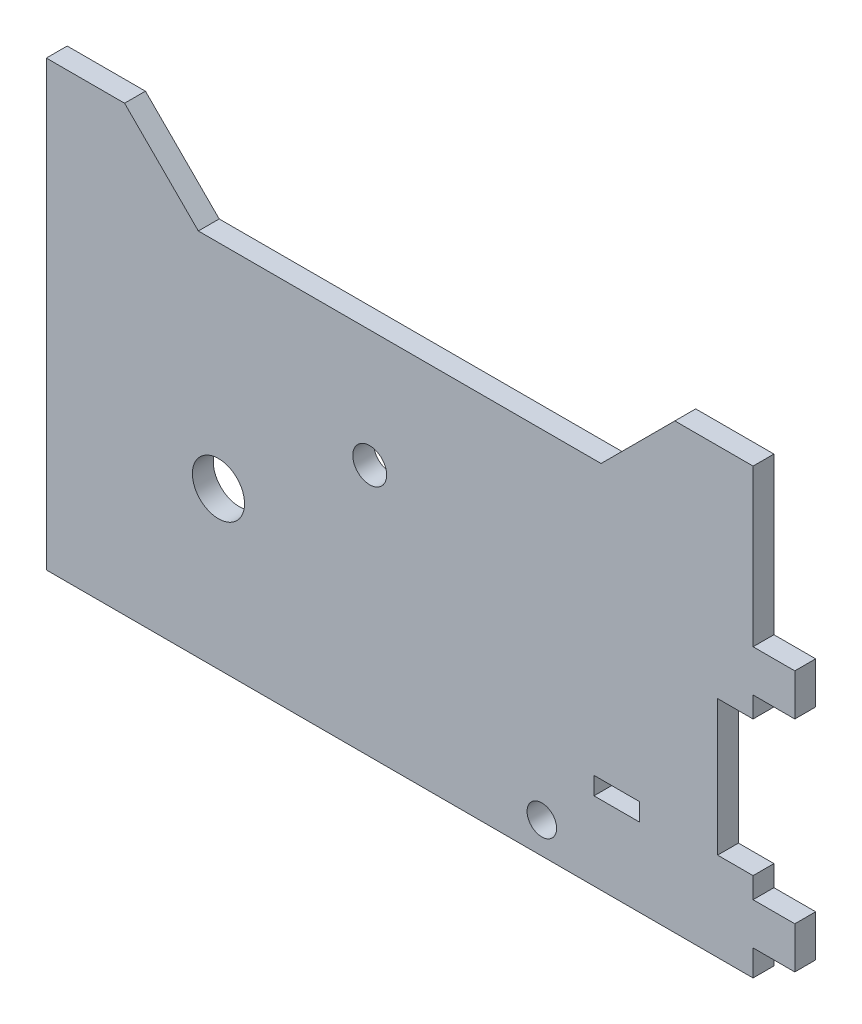
SolidWorks part; units mm, degrees
ref_plane "Front Plane" through (0, 0, 0) normal (0, 0, 1) x (1, 0, 0)
ref_plane "Top Plane" through (0, 0, 0) normal (0, 1, 0) x (1, 0, 0)
ref_plane "Right Plane" through (0, 0, 0) normal (1, 0, 0) x (0, 0, -1)
sketch "Sketch1" plane through (0, 0, 0) normal (0, 0, 1) x (1, 0, 0)
  line L0 (49, 30) -> (56.5, 30)
  line L1 (-79, -30) -> (49, -30)
  line L2 (-79, -30) -> (-79, 30)
  line L3 (-79, 30) -> (49, 30)
  line L6 (56.5, 13) -> (49.7, 13)
  line L7 (49.7, 13) -> (49.7, -13)
  line L8 (49.7, -13) -> (56.5, -13)
  line L10 (56.5, -30) -> (49, -30)
  line L11 (56.5, 30) -> (56.5, 13) construction
  line L12 (56.5, -13) -> (56.5, -30) construction
  line L13 (56.5, 30) -> (56.5, 25)
  line L14 (56.5, 25) -> (64.5, 25)
  line L15 (64.5, 25) -> (64.5, 17)
  line L16 (64.5, 17) -> (56.5, 17)
  line L17 (56.5, 17) -> (56.5, 13)
  line L18 (56.5, -13) -> (56.5, -17)
  line L19 (56.5, -17) -> (64.5, -17)
  line L20 (64.5, -17) -> (64.5, -25)
  line L21 (64.5, -25) -> (56.5, -25)
  line L22 (56.5, -25) -> (56.5, -30)
  line L23 (49, 30) -> (49, -30) construction
  line L24 (26, -11.6) -> (34.7, -11.6)
  line L25 (26, -11.6) -> (26, -15)
  line L26 (26, -15) -> (34.7, -15)
  line L27 (34.7, -11.6) -> (34.7, -15)
  circle A3 centre (-46, 0) radius 5
  circle A4 centre (16, -24) radius 2.83
  circle A5 centre (-17, 18.3961) radius 3.25
  point P1 (-12, 0)
  point P6 (0, 0)
  dimension "D3" = 128
  dimension "D4" = 6
  dimension "D5" = 10
  dimension "D1" = 33
  dimension "D7" = 5
  dimension "D17" = 5.66
  dimension "D18" = 95
  dimension "D25" = 6.5
  dimension "D27" = 29
  dimension "D28" = 18.3961
  dimension "D8" = 26
  dimension "D9" = 5
  dimension "D10" = 7.5
  dimension "D11" = 8
  dimension "D12" = 8
  dimension "D13" = 8.7
  dimension "D14" = 3.4
  dimension "D15" = 15
  dimension "D16" = 15
  dimension "D20" = 4
  dimension "D21" = 4
  dimension "D24" = 8
extrude "Boss-Extrude1" add sketch "Sketch1" along normal blind 4
sketch "Sketch2" plane through (0, 0, 0) normal (0, 0, 1) x (1, 0, 0)
  line L0 (-79, 30) -> (56.5, 30)
  line L1 (56.5, 30) -> (56.5, 55)
  line L2 (56.5, 55) -> (41.5, 55)
  line L3 (41.5, 55) -> (27.3579, 40.8579)
  line L4 (27.3579, 40.8579) -> (-49.8579, 40.8579)
  line L5 (-49.8579, 40.8579) -> (-64, 55)
  line L6 (-64, 55) -> (-79, 55)
  line L7 (-79, 55) -> (-79, 30)
  dimension "D1" = 25
  dimension "D2" = 15
  dimension "D3" = 20
  dimension "D4" = 135
extrude "Boss-Extrude2" add sketch "Sketch2" along normal blind 4
